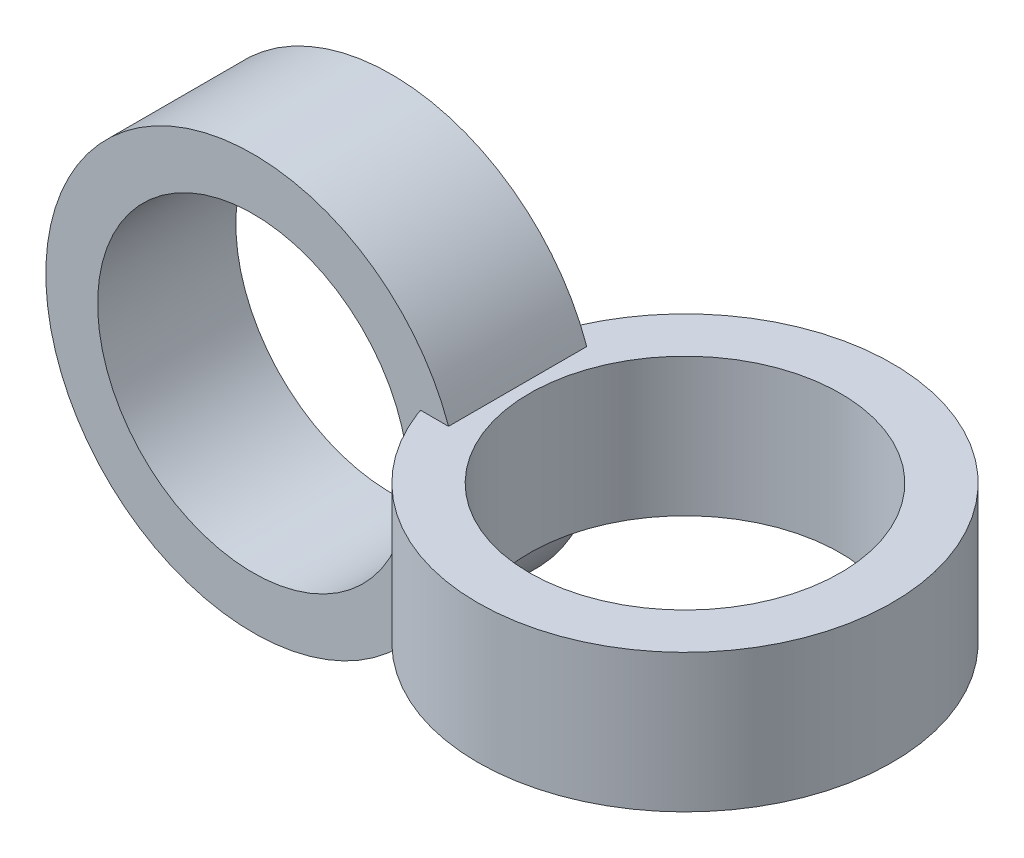
SolidWorks part; units mm, degrees
ref_plane "Front Plane" through (0, 0, 0) normal (0, 0, 1) x (1, 0, 0)
ref_plane "Top Plane" through (0, 0, 0) normal (0, 1, 0) x (1, 0, 0)
ref_plane "Right Plane" through (0, 0, 0) normal (1, 0, 0) x (0, 0, -1)
sketch "Sketch1" plane through (0, 0, 0) normal (0, 0, 1) x (1, 0, 0)
  circle A0 centre (0, 0) radius 96
  circle A1 centre (0, 0) radius 72
  dimension "D1" = 192
  dimension "D2" = 144
extrude "Boss-Extrude1" add sketch "Sketch1" along normal blind 32 and the other way blind 32
sketch "Sketch2" plane through (0, 0, 0) normal (0, 1, 0) x (1, 0, 0)
  circle A0 centre (168, 0) radius 96
  circle A1 centre (168, 0) radius 72
  dimension "D1" = 192
  dimension "D3" = 144
  dimension "D2" = 168
extrude "Boss-Extrude2" add sketch "Sketch2" along normal blind 32 and the other way blind 32 separate body
